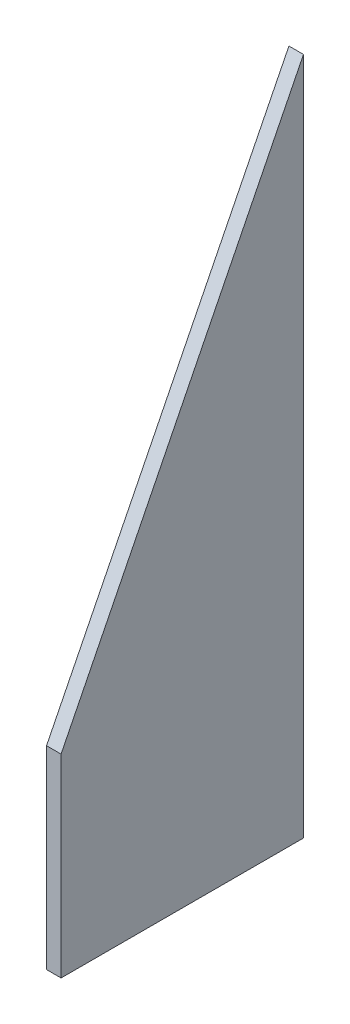
SolidWorks part; units mm, degrees
ref_plane "Front Plane" through (0, 0, 0) normal (0, 0, 1) x (1, 0, 0)
ref_plane "Top Plane" through (0, 0, 0) normal (0, 1, 0) x (1, 0, 0)
ref_plane "Right Plane" through (0, 0, 0) normal (1, 0, 0) x (0, 0, -1)
sketch "Sketch1" plane through (0, 0, 0) normal (1, 0, 0) x (0, 0, -1)
  line L0 (-33.9725, 0) -> (-83.9725, 0)
  line L1 (-83.9725, 0) -> (-83.9725, 40)
  line L2 (-83.9725, 40) -> (-33.9725, 140)
  line L3 (-33.9725, 140) -> (-33.9725, 0)
  dimension "D1" = 50
  dimension "D2" = 100
  dimension "D3" = 140
  dimension "D4" = 33.9725
extrude "Boss-Extrude1" add sketch "Sketch1" along normal mid plane 3
